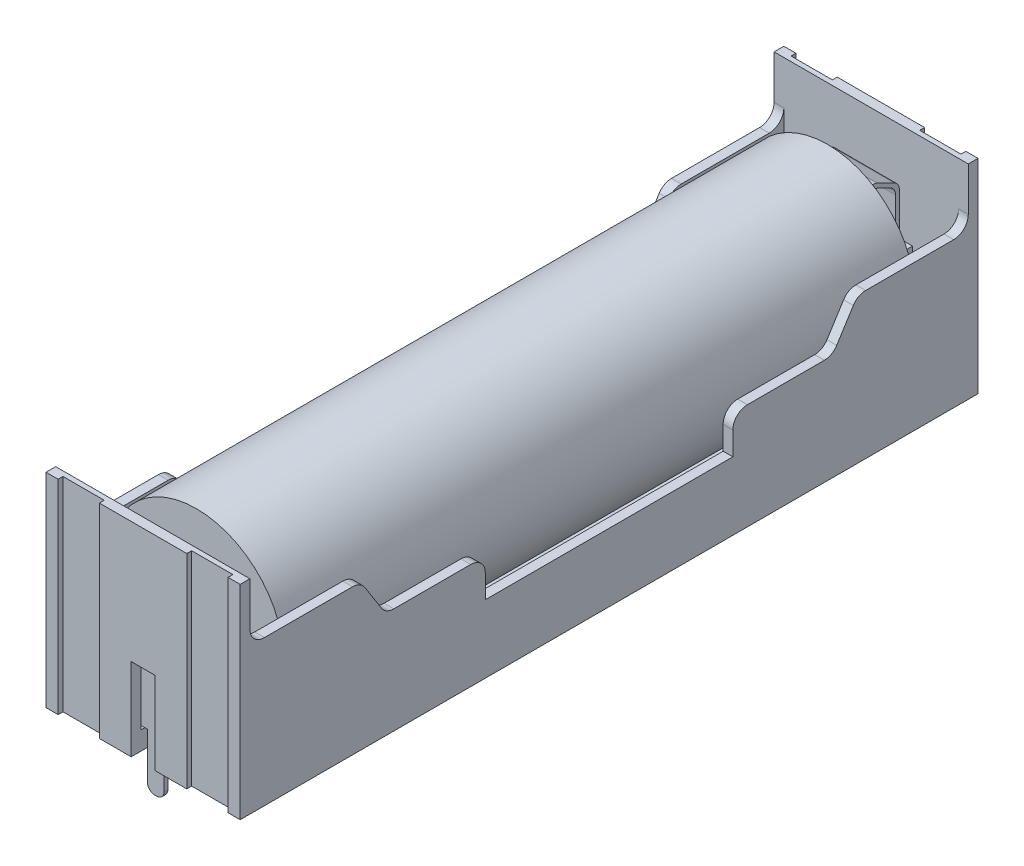
SolidWorks part; units mm, degrees
material "ABS"
ref_plane "Спереди" through (0, 0, 0) normal (0, 0, 1) x (1, 0, 0)
ref_plane "Сверху" through (0, 0, 0) normal (0, 1, 0) x (1, 0, 0)
ref_plane "Справа" through (0, 0, 0) normal (1, 0, 0) x (0, 0, -1)
other "Configuration Table"
sketch "Эскиз1" plane through (0, 0, 0) normal (0, 1, 0) x (1, 0, 0)
  line L1 (-10, 38) -> (10, 38)
  line L2 (-10, 38) -> (-10, -38)
  line L3 (-10, -38) -> (10, -38)
  line L4 (10, 38) -> (10, -38)
  line L5 (-10, 38) -> (10, -38) construction
  line L6 (-10, -38) -> (10, 38) construction
  point P0 (0, 0)
  dimension "D1" = 76
  dimension "D2" = 20
extrude "Основа" add sketch "Эскиз1" along normal blind 21
sketch "Эскиз2" plane through (0, 0, 0) normal (0, 1, 0) x (1, 0, 0)
  line L1 (10, 38) -> (-10, 38) construction
  line L2 (-4.5, 38) -> (-4.5, 37.5)
  line L3 (-4.5, 37.5) -> (-8.75, 37.5)
  line L4 (-8.75, 37.5) -> (-8.75, 38)
  line L5 (-8.75, 38) -> (-10.75, 38)
  line L6 (-10.75, 38) -> (-10.75, 37.5)
  line L13 (-10.75, 38) -> (-10, 38)
  line L14 (-10, 38) -> (-10, 46.5071)
  line L15 (-10, 46.5071) -> (10, 46.5071)
  line L16 (0, 46.5071) -> (0, 38)
  line L17 (4.5, 38) -> (-4.5, 38)
  line L18 (10, 38) -> (10, 46.5071)
  line L26 (10.75, 38) -> (10.75, 37.5)
  line L27 (8.75, 38) -> (10.75, 38)
  line L28 (4.5, 38) -> (4.5, 37.5)
  line L29 (4.5, 37.5) -> (8.75, 37.5)
  line L30 (8.75, 37.5) -> (8.75, 38)
  line L31 (10.75, 38) -> (10, 38)
  line L32 (-10.75, 37.5) -> (-8.75, 37.5)
  line L33 (10.75, 37.5) -> (8.75, 37.5)
  point P22 (0, 38)
  dimension "D1" = 9
  dimension "D2" = 2
  dimension "D3" = 4.25
  dimension "D4" = 0.5
extrude "Рёбра" cut sketch "Эскиз2" along normal through all contours L29 L30 L27 L26 L18 L15 L16 L17 L28 | L17 L16 L15 L14 L13 L6 L5 L4 L3 L2 region at (-5.0396, 0, -42.1438) region at (5.0396, 0, -42.1438)
mirror "Зеркальное отражение1" about plane through (0, 0, 0) normal (0, 0, 1) of "Рёбра"
sketch "Эскиз3" plane through (0, 21, 0) normal (0, 1, 0) x (1, 0, 0)
  line L0 (9, 0) -> (-9, 0) construction
  line L1 (9, 37) -> (-9, 37)
  line L2 (9, 37) -> (9, -37)
  line L3 (9, -37) -> (-9, -37)
  line L4 (-9, 37) -> (-9, -37)
  line L5 (9, 37) -> (-9, -37) construction
  line L6 (9, -37) -> (-9, 37) construction
  point P0 (0, 0)
  point P9 (0, 0)
  dimension "D1" = 18
  dimension "D2" = 74
extrude "Отсеки" cut sketch "Эскиз3" against normal blind 19.1
sketch "Эскиз4" plane through (0, 0, 0) normal (1, 0, 0) x (0, 0, -1)
  line L0 (37, 21) -> (-37, 21) construction
  line L1 (37, 27) -> (-37, 27)
  line L2 (37, 27) -> (37, 15)
  line L3 (37, 15) -> (-37, 15)
  line L4 (-37, 27) -> (-37, 15)
  line L5 (37, 27) -> (-37, 15) construction
  line L6 (37, 15) -> (-37, 27) construction
  line L7 (-37, 1.9) -> (-37, 21) construction
  point P0 (0, 21)
  dimension "D1" = 15
extrude "Уменьшение внутренних стенок" cut sketch "Эскиз4" against normal blind 15 and the other way blind 15
sketch "Эскиз5" plane through (10, 0, 0) normal (1, 0, 0) x (0, 0, -1)
  line L0 (-38, 21) -> (-35.6, 21)
  line L1 (-38, 21) -> (-37, 21) construction
  line L2 (-35.6, 21) -> (-35.6, 15)
  line L3 (-35.6, 15) -> (-25.6, 15)
  line L4 (-25.6, 15) -> (-23, 10.9)
  line L5 (-23, 10.9) -> (-12.75, 10.9)
  line L6 (-12.75, 10.9) -> (-12.75, 7)
  line L7 (-12.75, 7) -> (12.75, 7)
  line L8 (0, 7) -> (0, 0) construction
  line L9 (-35.6, 21) -> (35.6, 21)
  line L10 (12.75, 10.9) -> (12.75, 7)
  line L11 (23, 10.9) -> (12.75, 10.9)
  line L12 (25.6, 15) -> (23, 10.9)
  line L13 (35.6, 15) -> (25.6, 15)
  line L14 (35.6, 21) -> (35.6, 15)
  line L15 (-38, 21) -> (-37, 21) construction
  point P20 (0, 21)
  line M12 (38, 21) -> (37, 21)
  dimension "D1" = 12.75
  dimension "D2" = 10.25
  dimension "D3" = 2.4
  dimension "D4" = 10
  dimension "D5" = 6
  dimension "D6" = 3.9
  dimension "D7" = 7
extrude "Уменьшение внешних стенок" cut sketch "Эскиз5" against normal blind 15 contours L14 L2 L3 L4 L5 L6 L7 L10 L11 L12 L13 M12 region at (10, 15.384, 0)
fillet "Скругление2" radius 1.5 8 edges at (9.5, 10.9, -23) (9.5, 10.9, -12.75) (9.5, 10.9, 12.75) (9.5, 10.9, 23) (9.5, 15, -37) (9.5, 15, -25.6) (9.5, 15, 37) (9.5, 15, 25.6)
mirror "Зеркальное отражение2" about plane through (0, 0, 0) normal (1, 0, 0) of "Скругление2", "Уменьшение внешних стенок"
sketch "Эскиз6" plane through (0, 0, 0) normal (0, 1, 0) x (1, 0, 0)
  line L0 (-4.5, -38) -> (4.5, -38) construction
  line L1 (-1.225, -41.5) -> (1.225, -41.5)
  line L2 (-1.225, -41.5) -> (-1.225, -34.5)
  line L3 (-1.225, -34.5) -> (1.225, -34.5)
  line L4 (1.225, -41.5) -> (1.225, -34.5)
  line L5 (-1.225, -41.5) -> (1.225, -34.5) construction
  line L6 (-1.225, -34.5) -> (1.225, -41.5) construction
  line L7 (-10, 0) -> (10, 0) construction
  line L8 (10, -38) -> (10, 38) construction
  line L27 (-1.225, 34.5) -> (1.225, 41.5) construction
  line L28 (-1.225, 41.5) -> (1.225, 34.5) construction
  line L37 (1.225, 41.5) -> (1.225, 34.5)
  line L38 (-1.225, 34.5) -> (1.225, 34.5)
  line L39 (-1.225, 41.5) -> (-1.225, 34.5)
  line L40 (-1.225, 41.5) -> (1.225, 41.5)
  point P0 (0, -38)
  point P13 (0, 0)
  point P42 (0, 38)
  dimension "D1" = 2.45
  dimension "D2" = 3.5
extrude "Вырезы под контакты" cut sketch "Эскиз6" along normal blind 8.5
sketch "Эскиз11" plane through (0, 0, 0) normal (0, 1, 0) x (1, 0, 0)
  line L0 (0, 27.5) -> (0, -27.5) construction
  line L1 (1.5, -27.5) -> (-1.5, -27.5) construction
  line L3 (1.5, 27.5) -> (-1.5, 27.5) construction
  circle A1 centre (0, 27.5) radius 1.5
  circle A4 centre (0, -27.5) radius 1.5
  point P0 (0, 0)
  point P13 (0, 0)
  dimension "D2" = 3
  dimension "D1" = 55
extrude "Крепежные отверстия" cut sketch "Эскиз11" along normal through all
sketch "Эскиз12" plane through (0, 0, 0) normal (0, 1, 0) x (1, 0, 0)
  circle A1 centre (0, 27.5) radius 1.5 construction
  circle A4 centre (0, -27.5) radius 1.5 construction
  circle A7 centre (0, 27.5) radius 1.5
  circle A10 centre (0, -27.5) radius 1.5
  circle A13 centre (0, 27.5) radius 2.8
  circle A16 centre (0, -27.5) radius 2.8
  dimension "D1" = 1.3
extrude "Юбки отверстий" add sketch "Эскиз12" against normal blind 0.3
sketch "Эскиз13" plane through (0, 1.9, 0) normal (0, 1, 0) x (1, 0, 0)
  circle A1 centre (0, -27.5) radius 1.5 construction
  circle A3 centre (0, 27.5) radius 1.5 construction
  circle A6 centre (0, -27.5) radius 1.5
  circle A8 centre (0, 27.5) radius 1.5
  circle A13 centre (0, -27.5) radius 2.5
  circle A15 centre (0, 27.5) radius 2.5
  dimension "D1" = 1
extrude "Вырез-Вытянуть17" cut sketch "Эскиз13" against normal blind 0.5
sketch "Эскиз14" plane through (0, 1.9, 0) normal (0, 1, 0) x (1, 0, 0)
  line L0 (0, 20.5) -> (0, -20.5) construction
  line L3 (1.5, 20.5) -> (0, 20.5) construction
  line L4 (0, -20.5) -> (0, -19) construction
  line L5 (0, 19) -> (0, 20.5) construction
  line L8 (0.125, -19.2) -> (-0.125, -19.2)
  line L9 (0.125, -19.2) -> (0.125, -21.8)
  line L10 (0.125, -21.8) -> (-0.125, -21.8)
  line L11 (-0.125, -19.2) -> (-0.125, -21.8)
  line L12 (0.125, -19.2) -> (-0.125, -21.8) construction
  line L13 (0.125, -21.8) -> (-0.125, -19.2) construction
  line L14 (0.125, 21.8) -> (-0.125, 21.8)
  line L15 (0.125, 21.8) -> (0.125, 19.2)
  line L16 (0.125, 19.2) -> (-0.125, 19.2)
  line L17 (-0.125, 21.8) -> (-0.125, 19.2)
  line L18 (0.125, 21.8) -> (-0.125, 19.2) construction
  line L19 (0.125, 19.2) -> (-0.125, 21.8) construction
  line L20 (1.3, 20.625) -> (-1.3, 20.625)
  line L21 (1.3, 20.625) -> (1.3, 20.375)
  line L22 (1.3, 20.375) -> (-1.3, 20.375)
  line L23 (-1.3, 20.625) -> (-1.3, 20.375)
  line L24 (1.3, 20.625) -> (-1.3, 20.375) construction
  line L25 (1.3, 20.375) -> (-1.3, 20.625) construction
  circle A0 centre (0, 20.5) radius 1.5
  circle A1 centre (0, -20.5) radius 1.5
  point P0 (0, 0)
  point P2 (0, 0)
  dimension "D2" = 3
  dimension "D3" = 2.6
  dimension "D4" = 0.25
  dimension "D5" = 41
extrude "Полярность" cut sketch "Эскиз14" against normal blind 0.1 contours A1 L11 L8 L9 L10 | A0 L23 L20 L17 L14 L15 L21 L22 L16 region at (-1.4576, 1.9, -20.5) region at (-1.4576, 1.9, 20.5)
sketch "Эскиз15" plane through (0, 1.9, 0) normal (0, 1, 0) x (1, 0, 0)
  line L0 (-1.225, 37) -> (-9, 37) construction
  line L1 (-1.225, 37) -> (-1.225, 34.5) construction
  line L16 (-2.25, 35) -> (-4.25, 35)
  line L17 (-4.25, 35) -> (-4.25, 37)
  line L18 (-4.25, 37) -> (-3.25, 37)
  line L19 (-3.25, 37) -> (-3.25, 36)
  line L20 (-3.25, 36) -> (-2.25, 36)
  line L21 (-2.25, 36) -> (-2.25, 35)
  line L22 (2.25, 35) -> (2.25, 36)
  line L23 (2.25, 36) -> (3.25, 36)
  line L24 (3.25, 36) -> (3.25, 37)
  line L25 (3.25, 37) -> (4.25, 37)
  line L26 (4.25, 37) -> (4.25, 35)
  line L27 (4.25, 35) -> (2.25, 35)
  line L28 (0, 35.5) -> (0, 35) construction
  line L29 (-2.25, 35) -> (2.25, 35) construction
  line L44 (10, 0) -> (-10, 0) construction
  line L45 (-10, -12.75) -> (-10, 12.75) construction
  line L48 (-2.25, -35) -> (2.25, -35) construction
  line L49 (0, -35.5) -> (0, -35) construction
  line L64 (4.25, -35) -> (2.25, -35)
  line L65 (4.25, -37) -> (4.25, -35)
  line L66 (3.25, -37) -> (4.25, -37)
  line L67 (3.25, -36) -> (3.25, -37)
  line L68 (2.25, -36) -> (3.25, -36)
  line L69 (2.25, -35) -> (2.25, -36)
  line L70 (-2.25, -36) -> (-2.25, -35)
  line L71 (-3.25, -36) -> (-2.25, -36)
  line L72 (-3.25, -37) -> (-3.25, -36)
  line L73 (-4.25, -37) -> (-3.25, -37)
  line L74 (-4.25, -35) -> (-4.25, -37)
  line L75 (-2.25, -35) -> (-4.25, -35)
  point P4 (19.5, 35)
  point P24 (0, 35)
  point P55 (0, 0)
  point P99 (0, -35)
  dimension "D1" = 2
  dimension "D2" = 1.025
  dimension "D4" = 8.5
extrude "Пазы для контактов" add sketch "Эскиз15" along normal blind 8.9
ref_plane "Для эскиза контактов" through (0, 0, 0) normal (-1, 0, 0) x (0, 0, 1)
sketch "Эскиз16" plane through (0, 0, 0) normal (-1, 0, 0) x (0, 0, 1)
  line L1 (-38, 21) -> (-38, 0) construction
  line L3 (-36.5, 17.26) -> (-36.5, 15.9523) construction
  line L4 (-36.5, 15.9523) -> (-33.8, 17.26)
  line L5 (-33.8, 17.26) -> (-30.8, 13.9059)
  line L6 (-30.8, 13.9059) -> (-30.5, 9.4159)
  line L7 (-36.5, 17.26) -> (-33.8, 17.26) construction
  line L8 (-36.5, 15.9523) -> (-36.5, 2)
  line L10 (-36.5, 2) -> (-36.5, -3.54) construction
  line L12 (-38, 0) -> (38, 0) construction
  dimension "D1" = 20.8
  dimension "D2" = 3
  dimension "D3" = 4.5
  dimension "D4" = 6
  dimension "D5" = 5.7
  dimension "D6" = 2.7
  dimension "D7" = 2
  dimension "D8" = 1.5
  dimension "D9" = 13.9523
extrude "Контакт" add sketch "Эскиз16" along normal mid plane 6.4 thin thin type mid plane wall 0.4
sketch "Эскиз17" plane through (0, 2, 0) normal (0, -1, 0) x (1, 0, 0)
  line L0 (0, -36.7) -> (0, -36.3) construction
  line L1 (-3.2, -36.7) -> (3.2, -36.7) construction
  line L2 (-3.2, -36.3) -> (3.2, -36.3) construction
  line L4 (0.85, -36.3) -> (-0.85, -36.3)
  line L5 (0.85, -36.3) -> (0.85, -36.7)
  line L6 (0.85, -36.7) -> (-0.85, -36.7)
  line L7 (-0.85, -36.3) -> (-0.85, -36.7)
  line L8 (0.85, -36.3) -> (-0.85, -36.7) construction
  line L9 (0.85, -36.7) -> (-0.85, -36.3) construction
  point P6 (0, -36.5)
  dimension "D1" = 1.7
extrude "Штырёк для пайки" add sketch "Эскиз17" along normal blind 5.5
fillet "Скругление3" radius 1 6 edges at (0, 13.8239, -30.995) (0, 13.9879, -30.605) (0, 17.0143, -33.8485) (0, 17.5057, -33.7515) (0, 15.827, -36.3) (0, 16.0777, -36.7)
fillet "Скругление4" radius 0.75 6 edges at (3.2, 2, -36.5) (0.85, -3.5, -36.5) (-0.85, -3.5, -36.5) (-3.2, 2, -36.5) (3.2, 9.4159, -30.5) (-3.2, 9.4159, -30.5)
mirror "Mirror1" about plane through (0, 0, 0) normal (0, 0, 1) of bodies 125
sketch "Эскиз18" plane through (0, 0, 0) normal (0, 0, 1) x (1, 0, 0)
  circle A0 centre (0, 11) radius 9
  dimension "D1" = 18
  dimension "D2" = 11
extrude "Бобышка-Вытянуть1" add sketch "Эскиз18" along normal mid plane 65
equation "\"D1@Эскиз5\"=25.5/2"
